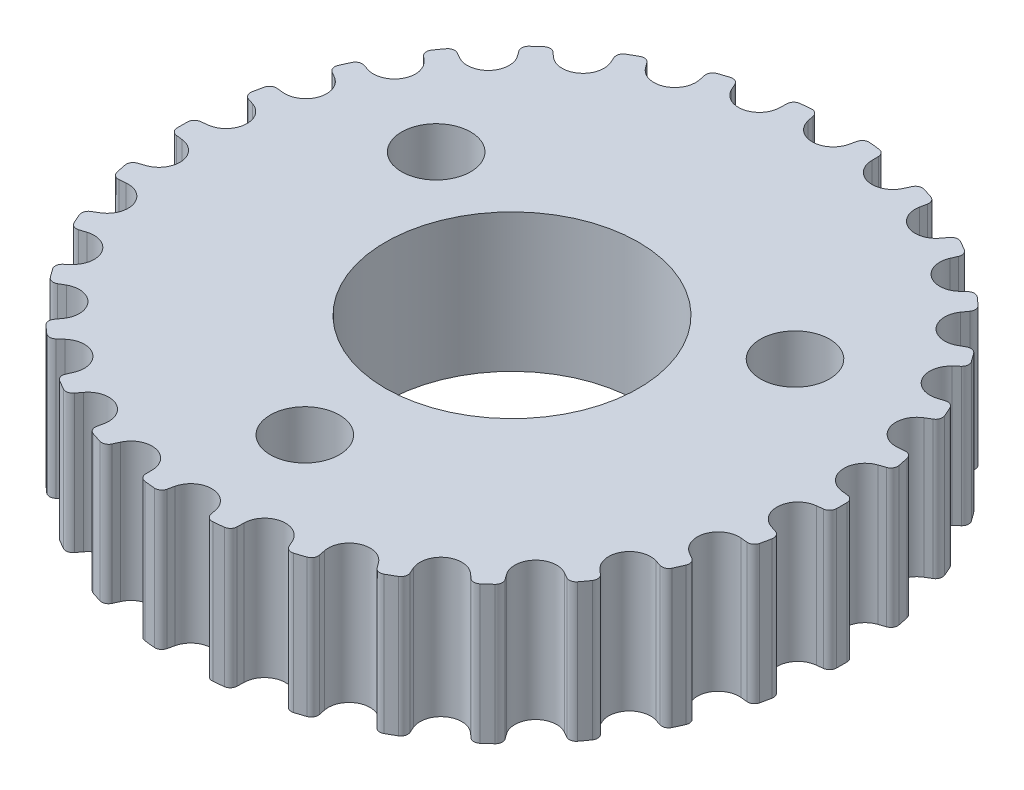
SolidWorks part; units mm, degrees
material "Acrylic (Medium-high impact)"
ref_plane "Front Plane" through (0, 0, 0) normal (0, 0, 1) x (1, 0, 0)
ref_plane "Top Plane" through (0, 0, 0) normal (0, 1, 0) x (1, 0, 0)
ref_plane "Right Plane" through (0, 0, 0) normal (1, 0, 0) x (0, 0, -1)
sketch "Sketch1" plane through (0, 0, 0) normal (0, 1, 0) x (1, 0, 0)
  circle A0 centre (0, 0) radius 14.3239
  dimension "D1" = 28.6479
extrude "Boss-Extrude1" add sketch "Sketch1" along normal blind 6
sketch "Sketch2" plane through (0, 6, 0) normal (0, 1, 0) x (1, 0, 0)
  line L0 (0, 0) -> (0, 14.3239) construction
  line L1 (-0.8883, 13.7564) -> (-0.95, 14.0339)
  line L2 (-2.9781, 14.0109) -> (-2.9781, 14.3239)
  line L3 (-2.9781, 14.3239) -> (2.9781, 14.3239)
  line L4 (0.8883, 13.7564) -> (0.95, 14.0339)
  line L5 (2.9781, 14.0109) -> (2.9781, 14.3239)
  circle A0 centre (0, 0) radius 14.3239 construction
  arc A1 (0.8883, 13.7564) -> (-0.8883, 13.7564) centre (0, 13.9539) cw
  arc A2 (-0.95, 14.0339) -> (-1.2694, 14.2676) centre (-1.2428, 13.9688) ccw
  arc A4 (0.95, 14.0339) -> (1.2694, 14.2676) centre (1.2428, 13.9688) cw
  arc A5 (-1.2694, 14.2676) -> (-2.9781, 14.0109) centre (0, 0) ccw
  arc A6 (1.2694, 14.2676) -> (2.9781, 14.0109) centre (0, 0) cw
  circle A8 centre (0, 0) radius 14.3239 construction
  point P11 (0, 14.3239)
  point P19 (0, 13.0439)
  dimension "D3" = 0.3
  dimension "D5" = 0.91
  dimension "D2" = 0.95
  dimension "D4" = 1.28
  dimension "D6" = 12
extrude "Cut-Extrude1" cut sketch "Sketch2" against normal through all
pattern_circular "CirPattern1" count 30 over 360 about axis through (0, 6, 0) along (0, -1, 0) of "Cut-Extrude1"
sketch "Sketch3" plane through (0, 0, 0) normal (0, -1, 0) x (1, 0, 0)
  circle A0 centre (0, 0) radius 5.5
  dimension "D1" = 11
extrude "Cut-Extrude2" cut sketch "Sketch3" against normal through all
sketch "Sketch4" plane through (0, 0, 0) normal (0, -1, 0) x (1, 0, 0)
  line L0 (0, 0) -> (0, 9) construction
  circle A0 centre (0, 9) radius 1.5
  circle A1 centre (7.7942, -4.5) radius 1.5
  circle A2 centre (-7.7942, -4.5) radius 1.5
  point P14 (0, 0)
  dimension "D1" = 3
  dimension "D2" = 9
  dimension "D3" = 3
extrude "Cut-Extrude3" cut sketch "Sketch4" against normal through all
sketch "Sketch5" plane through (0, 0, 0) normal (0, -1, 0) x (1, 0, 0)
  line L60 (8.7383, -10.682) -> (8.9513, -10.8702)
  line L61 (8.7383, -10.682) -> (8.9513, -10.8702)
  line L62 (9.875, -10.0385) -> (9.7101, -9.807)
  line L63 (9.875, -10.0385) -> (9.7101, -9.807)
  line L64 (12.5987, 6.2896) -> (12.3276, 6.2043)
  line L65 (12.5987, 6.2896) -> (12.3276, 6.2043)
  line L66 (11.5369, 7.5738) -> (11.7463, 7.766)
  line L67 (11.5369, 7.5738) -> (11.7463, 7.766)
  line L68 (-3.638, 13.3126) -> (-3.7561, 13.5712)
  line L69 (-3.638, 13.3126) -> (-3.7561, 13.5712)
  line L70 (-4.9382, 13.1871) -> (-4.8817, 12.9085)
  line L71 (-4.9382, 13.1871) -> (-4.8817, 12.9085)
  line L72 (-11.7463, 7.766) -> (-11.5369, 7.5738)
  line L73 (-11.7463, 7.766) -> (-11.5369, 7.5738)
  line L74 (-12.3276, 6.2043) -> (-12.5987, 6.2896)
  line L75 (-12.3276, 6.2043) -> (-12.5987, 6.2896)
  line L76 (-13.1043, 5.1541) -> (-12.8594, 5.0097)
  line L77 (-13.1043, 5.1541) -> (-12.8594, 5.0097)
  line L78 (-13.3481, 3.5057) -> (-13.6311, 3.5327)
  line L79 (-13.3481, 3.5057) -> (-13.6311, 3.5327)
  line L80 (-13.8895, 2.3169) -> (-13.62, 2.2266)
  line L81 (-13.8895, 2.3169) -> (-13.62, 2.2266)
  line L82 (-13.7853, 0.6538) -> (-14.0677, 0.6215)
  line L83 (-13.7853, 0.6538) -> (-14.0677, 0.6215)
  line L84 (-14.0677, -0.6215) -> (-13.7853, -0.6538)
  line L85 (-14.0677, -0.6215) -> (-13.7853, -0.6538)
  line L86 (-13.62, -2.2266) -> (-13.8895, -2.3169)
  line L87 (-13.62, -2.2266) -> (-13.8895, -2.3169)
  line L88 (-13.6311, -3.5327) -> (-13.3481, -3.5057)
  line L89 (-13.6311, -3.5327) -> (-13.3481, -3.5057)
  line L90 (-12.8594, -5.0097) -> (-13.1043, -5.1541)
  line L91 (-12.8594, -5.0097) -> (-13.1043, -5.1541)
  line L92 (-12.5987, -6.2896) -> (-12.3276, -6.2043)
  line L93 (-12.5987, -6.2896) -> (-12.3276, -6.2043)
  line L94 (-11.5369, -7.5738) -> (-11.7463, -7.766)
  line L95 (-11.5369, -7.5738) -> (-11.7463, -7.766)
  line L96 (-11.0157, -8.7716) -> (-10.7682, -8.6318)
  line L97 (-11.0157, -8.7716) -> (-10.7682, -8.6318)
  line L98 (-9.7101, -9.807) -> (-9.875, -10.0385)
  line L99 (-9.7101, -9.807) -> (-9.875, -10.0385)
  line L100 (-8.9513, -10.8702) -> (-8.7383, -10.682)
  line L101 (-8.9513, -10.8702) -> (-8.7383, -10.682)
  line L102 (-7.4589, -11.6115) -> (-7.5721, -11.8722)
  line L103 (-7.4589, -11.6115) -> (-7.5721, -11.8722)
  line L104 (-6.4956, -12.4937) -> (-6.3264, -12.2653)
  line L105 (-6.4956, -12.4937) -> (-6.3264, -12.2653)
  line L106 (-4.8817, -12.9085) -> (-4.9382, -13.1871)
  line L107 (-4.8817, -12.9085) -> (-4.9382, -13.1871)
  line L108 (-3.7561, -13.5712) -> (-3.638, -13.3126)
  line L109 (-3.7561, -13.5712) -> (-3.638, -13.3126)
  line L110 (-2.0912, -13.6414) -> (-2.0886, -13.9257)
  line L111 (-2.0912, -13.6414) -> (-2.0886, -13.9257)
  line L120 (6.3264, -12.2653) -> (6.4956, -12.4937)
  line L121 (7.5721, -11.8722) -> (7.4589, -11.6115)
  line L124 (10.7682, -8.6318) -> (11.0157, -8.7716)
  line L125 (11.7463, -7.766) -> (11.5369, -7.5738)
  line L126 (12.3276, -6.2043) -> (12.5987, -6.2896)
  line L127 (13.1043, -5.1541) -> (12.8594, -5.0097)
  line L128 (13.3481, -3.5057) -> (13.6311, -3.5327)
  line L129 (13.8895, -2.3169) -> (13.62, -2.2266)
  line L130 (13.7853, -0.6538) -> (14.0677, -0.6215)
  line L131 (14.0677, 0.6215) -> (13.7853, 0.6538)
  line L132 (13.62, 2.2266) -> (13.8895, 2.3169)
  line L133 (13.6311, 3.5327) -> (13.3481, 3.5057)
  line L134 (12.8594, 5.0097) -> (13.1043, 5.1541)
  line L137 (11.0157, 8.7716) -> (10.7682, 8.6318)
  line L138 (9.7101, 9.807) -> (9.875, 10.0385)
  line L139 (8.9513, 10.8702) -> (8.7383, 10.682)
  line L140 (7.4589, 11.6115) -> (7.5721, 11.8722)
  line L141 (6.4956, 12.4937) -> (6.3264, 12.2653)
  line L142 (4.8817, 12.9085) -> (4.9382, 13.1871)
  line L143 (3.7561, 13.5712) -> (3.638, 13.3126)
  line L144 (2.0912, 13.6414) -> (2.0886, 13.9257)
  line L145 (0.8524, 14.0556) -> (0.7907, 13.7781)
  line L146 (-0.7907, 13.7781) -> (-0.8524, 14.0556)
  line L147 (-2.0886, 13.9257) -> (-2.0912, 13.6414)
  line L150 (-6.3264, 12.2653) -> (-6.4956, 12.4937)
  line L151 (-7.5721, 11.8722) -> (-7.4589, 11.6115)
  line L152 (-8.7383, 10.682) -> (-8.9513, 10.8702)
  line L153 (-9.875, 10.0385) -> (-9.7101, 9.807)
  line L154 (-10.7682, 8.6318) -> (-11.0157, 8.7716)
  line L175 (-0.8524, -14.0556) -> (-0.7907, -13.7781)
  line L176 (0.7907, -13.7781) -> (0.8524, -14.0556)
  line L177 (2.0886, -13.9257) -> (2.0912, -13.6414)
  line L178 (3.638, -13.3126) -> (3.7561, -13.5712)
  line L179 (4.9382, -13.1871) -> (4.8817, -12.9085)
  line L180 (6.3264, -12.2653) -> (6.4956, -12.4937)
  line L181 (7.5721, -11.8722) -> (7.4589, -11.6115)
  line L184 (10.7682, -8.6318) -> (11.0157, -8.7716)
  line L185 (11.7463, -7.766) -> (11.5369, -7.5738)
  line L186 (12.3276, -6.2043) -> (12.5987, -6.2896)
  line L187 (13.1043, -5.1541) -> (12.8594, -5.0097)
  line L188 (13.3481, -3.5057) -> (13.6311, -3.5327)
  line L189 (13.8895, -2.3169) -> (13.62, -2.2266)
  line L190 (13.7853, -0.6538) -> (14.0677, -0.6215)
  line L191 (14.0677, 0.6215) -> (13.7853, 0.6538)
  line L192 (13.62, 2.2266) -> (13.8895, 2.3169)
  line L193 (13.6311, 3.5327) -> (13.3481, 3.5057)
  line L194 (12.8594, 5.0097) -> (13.1043, 5.1541)
  line L197 (11.0157, 8.7716) -> (10.7682, 8.6318)
  line L198 (9.7101, 9.807) -> (9.875, 10.0385)
  line L199 (8.9513, 10.8702) -> (8.7383, 10.682)
  line L200 (7.4589, 11.6115) -> (7.5721, 11.8722)
  line L201 (6.4956, 12.4937) -> (6.3264, 12.2653)
  line L202 (4.8817, 12.9085) -> (4.9382, 13.1871)
  line L203 (3.7561, 13.5712) -> (3.638, 13.3126)
  line L204 (2.0912, 13.6414) -> (2.0886, 13.9257)
  line L205 (0.8524, 14.0556) -> (0.7907, 13.7781)
  line L206 (-0.7907, 13.7781) -> (-0.8524, 14.0556)
  line L207 (-2.0886, 13.9257) -> (-2.0912, 13.6414)
  line L210 (-6.3264, 12.2653) -> (-6.4956, 12.4937)
  line L211 (-7.5721, 11.8722) -> (-7.4589, 11.6115)
  line L212 (-8.7383, 10.682) -> (-8.9513, 10.8702)
  line L213 (-9.875, 10.0385) -> (-9.7101, 9.807)
  line L214 (-10.7682, 8.6318) -> (-11.0157, 8.7716)
  line L235 (-0.8524, -14.0556) -> (-0.7907, -13.7781)
  line L236 (0.7907, -13.7781) -> (0.8524, -14.0556)
  line L237 (2.0886, -13.9257) -> (2.0912, -13.6414)
  line L238 (3.638, -13.3126) -> (3.7561, -13.5712)
  line L239 (4.9382, -13.1871) -> (4.8817, -12.9085)
  arc A76 (8.9513, -10.8702) -> (9.479, -10.8719) centre (9.2161, -10.5704) ccw
  arc A77 (8.9513, -10.8702) -> (9.479, -10.8719) centre (9.2161, -10.5704) ccw
  arc A78 (9.479, -10.8719) -> (9.8216, -10.5635) centre (0, 0) ccw
  arc A79 (9.479, -10.8719) -> (9.8216, -10.5635) centre (0, 0) ccw
  arc A80 (9.8216, -10.5635) -> (9.875, -10.0385) centre (9.5492, -10.2705) ccw
  arc A81 (9.8216, -10.5635) -> (9.875, -10.0385) centre (9.5492, -10.2705) ccw
  circle A120 centre (0, 0) radius 13.0439
  arc A121 (-0.8883, 13.7564) -> (0.8883, 13.7564) centre (0, 13.9539) ccw construction
  arc A128 (11.5369, 7.5738) -> (12.3276, 6.2043) centre (12.0845, 6.977) ccw
  arc A129 (11.5369, 7.5738) -> (12.3276, 6.2043) centre (12.0845, 6.977) ccw
  arc A130 (-3.7561, 13.5712) -> (-4.2375, 13.7875) centre (-4.12, 13.4051) ccw
  arc A131 (-3.7561, 13.5712) -> (-4.2375, 13.7875) centre (-4.12, 13.4051) ccw
  arc A132 (-4.2375, 13.7875) -> (-4.6759, 13.645) centre (0, 0) ccw
  arc A133 (-4.2375, 13.7875) -> (-4.6759, 13.645) centre (0, 0) ccw
  arc A134 (-4.6759, 13.645) -> (-4.9382, 13.1871) centre (-4.5462, 13.2666) ccw
  arc A135 (-4.6759, 13.645) -> (-4.9382, 13.1871) centre (-4.5462, 13.2666) ccw
  arc A136 (-11.8032, 8.2906) -> (-11.7463, 7.766) centre (-11.4759, 8.0607) ccw
  arc A137 (-11.8032, 8.2906) -> (-11.7463, 7.766) centre (-11.4759, 8.0607) ccw
  arc A138 (-12.3276, 6.2043) -> (-11.5369, 7.5738) centre (-12.0845, 6.977) ccw
  arc A139 (-12.3276, 6.2043) -> (-11.5369, 7.5738) centre (-12.0845, 6.977) ccw
  arc A140 (-12.5987, 6.2896) -> (-13.0815, 6.0766) centre (-12.7187, 5.908) ccw
  arc A141 (-12.5987, 6.2896) -> (-13.0815, 6.0766) centre (-12.7187, 5.908) ccw
  arc A142 (-13.0815, 6.0766) -> (-13.269, 5.6554) centre (0, 0) ccw
  arc A143 (-13.0815, 6.0766) -> (-13.269, 5.6554) centre (0, 0) ccw
  arc A144 (-13.269, 5.6554) -> (-13.1043, 5.1541) centre (-12.901, 5.4986) ccw
  arc A145 (-13.269, 5.6554) -> (-13.1043, 5.1541) centre (-12.901, 5.4986) ccw
  arc A146 (-13.3481, 3.5057) -> (-12.8594, 5.0097) centre (-13.271, 4.312) ccw
  arc A147 (-13.3481, 3.5057) -> (-12.8594, 5.0097) centre (-13.271, 4.312) ccw
  arc A148 (-13.6311, 3.5327) -> (-14.059, 3.224) centre (-13.6691, 3.1346) ccw
  arc A149 (-13.6311, 3.5327) -> (-14.059, 3.224) centre (-13.6691, 3.1346) ccw
  arc A150 (-14.059, 3.224) -> (-14.1549, 2.7731) centre (0, 0) ccw
  arc A151 (-14.059, 3.224) -> (-14.1549, 2.7731) centre (0, 0) ccw
  arc A152 (-14.1549, 2.7731) -> (-13.8895, 2.3169) centre (-13.7623, 2.6962) ccw
  arc A153 (-14.1549, 2.7731) -> (-13.8895, 2.3169) centre (-13.7623, 2.6962) ccw
  arc A154 (-13.7853, 0.6538) -> (-13.62, 2.2266) centre (-13.8775, 1.4586) ccw
  arc A155 (-13.7853, 0.6538) -> (-13.62, 2.2266) centre (-13.8775, 1.4586) ccw
  arc A156 (-14.0677, 0.6215) -> (-14.4221, 0.2305) centre (-14.0222, 0.2241) ccw
  arc A157 (-14.0677, 0.6215) -> (-14.4221, 0.2305) centre (-14.0222, 0.2241) ccw
  arc A158 (-14.4221, 0.2305) -> (-14.4221, -0.2305) centre (0, 0) ccw
  arc A159 (-14.4221, 0.2305) -> (-14.4221, -0.2305) centre (0, 0) ccw
  arc A160 (-14.4221, -0.2305) -> (-14.0677, -0.6215) centre (-14.0222, -0.2241) ccw
  arc A161 (-14.4221, -0.2305) -> (-14.0677, -0.6215) centre (-14.0222, -0.2241) ccw
  arc A162 (-13.62, -2.2266) -> (-13.7853, -0.6538) centre (-13.8775, -1.4586) ccw
  arc A163 (-13.62, -2.2266) -> (-13.7853, -0.6538) centre (-13.8775, -1.4586) ccw
  arc A164 (-13.8895, -2.3169) -> (-14.1549, -2.7731) centre (-13.7623, -2.6962) ccw
  arc A165 (-13.8895, -2.3169) -> (-14.1549, -2.7731) centre (-13.7623, -2.6962) ccw
  arc A166 (-14.1549, -2.7731) -> (-14.059, -3.224) centre (0, 0) ccw
  arc A167 (-14.1549, -2.7731) -> (-14.059, -3.224) centre (0, 0) ccw
  arc A168 (-14.059, -3.224) -> (-13.6311, -3.5327) centre (-13.6691, -3.1346) ccw
  arc A169 (-14.059, -3.224) -> (-13.6311, -3.5327) centre (-13.6691, -3.1346) ccw
  arc A170 (-12.8594, -5.0097) -> (-13.3481, -3.5057) centre (-13.271, -4.312) ccw
  arc A171 (-12.8594, -5.0097) -> (-13.3481, -3.5057) centre (-13.271, -4.312) ccw
  arc A172 (-13.1043, -5.1541) -> (-13.269, -5.6554) centre (-12.901, -5.4986) ccw
  arc A173 (-13.1043, -5.1541) -> (-13.269, -5.6554) centre (-12.901, -5.4986) ccw
  arc A174 (-13.269, -5.6554) -> (-13.0815, -6.0766) centre (0, 0) ccw
  arc A175 (-13.269, -5.6554) -> (-13.0815, -6.0766) centre (0, 0) ccw
  arc A176 (-13.0815, -6.0766) -> (-12.5987, -6.2896) centre (-12.7187, -5.908) ccw
  arc A177 (-13.0815, -6.0766) -> (-12.5987, -6.2896) centre (-12.7187, -5.908) ccw
  arc A178 (-11.5369, -7.5738) -> (-12.3276, -6.2043) centre (-12.0845, -6.977) ccw
  arc A179 (-11.5369, -7.5738) -> (-12.3276, -6.2043) centre (-12.0845, -6.977) ccw
  arc A180 (-11.7463, -7.766) -> (-11.8032, -8.2906) centre (-11.4759, -8.0607) ccw
  arc A181 (-11.7463, -7.766) -> (-11.8032, -8.2906) centre (-11.4759, -8.0607) ccw
  arc A182 (-11.8032, -8.2906) -> (-11.5323, -8.6636) centre (0, 0) ccw
  arc A183 (-11.8032, -8.2906) -> (-11.5323, -8.6636) centre (0, 0) ccw
  arc A184 (-11.5323, -8.6636) -> (-11.0157, -8.7716) centre (-11.2124, -8.4233) ccw
  arc A185 (-11.5323, -8.6636) -> (-11.0157, -8.7716) centre (-11.2124, -8.4233) ccw
  arc A186 (-9.7101, -9.807) -> (-10.7682, -8.6318) centre (-10.3698, -9.337) ccw
  arc A187 (-9.7101, -9.807) -> (-10.7682, -8.6318) centre (-10.3698, -9.337) ccw
  arc A188 (-9.875, -10.0385) -> (-9.8216, -10.5635) centre (-9.5492, -10.2705) ccw
  arc A189 (-9.875, -10.0385) -> (-9.8216, -10.5635) centre (-9.5492, -10.2705) ccw
  arc A190 (-9.8216, -10.5635) -> (-9.479, -10.8719) centre (0, 0) ccw
  arc A191 (-9.8216, -10.5635) -> (-9.479, -10.8719) centre (0, 0) ccw
  arc A192 (-9.479, -10.8719) -> (-8.9513, -10.8702) centre (-9.2161, -10.5704) ccw
  arc A193 (-9.479, -10.8719) -> (-8.9513, -10.8702) centre (-9.2161, -10.5704) ccw
  arc A194 (-7.4589, -11.6115) -> (-8.7383, -10.682) centre (-8.2019, -11.289) ccw
  arc A195 (-7.4589, -11.6115) -> (-8.7383, -10.682) centre (-8.2019, -11.289) ccw
  arc A196 (-7.5721, -11.8722) -> (-7.4107, -12.3747) centre (-7.2051, -12.0315) ccw
  arc A197 (-7.5721, -11.8722) -> (-7.4107, -12.3747) centre (-7.2051, -12.0315) ccw
  arc A198 (-7.4107, -12.3747) -> (-7.0114, -12.6052) centre (0, 0) ccw
  arc A199 (-7.4107, -12.3747) -> (-7.0114, -12.6052) centre (0, 0) ccw
  arc A200 (-7.0114, -12.6052) -> (-6.4956, -12.4937) centre (-6.817, -12.2556) ccw
  arc A201 (-7.0114, -12.6052) -> (-6.4956, -12.4937) centre (-6.817, -12.2556) ccw
  arc A202 (-4.8817, -12.9085) -> (-6.3264, -12.2653) centre (-5.6756, -12.7476) ccw
  arc A203 (-4.8817, -12.9085) -> (-6.3264, -12.2653) centre (-5.6756, -12.7476) ccw
  arc A204 (-4.9382, -13.1871) -> (-4.6759, -13.645) centre (-4.5462, -13.2666) ccw
  arc A205 (-4.9382, -13.1871) -> (-4.6759, -13.645) centre (-4.5462, -13.2666) ccw
  arc A206 (-4.6759, -13.645) -> (-4.2375, -13.7875) centre (0, 0) ccw
  arc A207 (-4.6759, -13.645) -> (-4.2375, -13.7875) centre (0, 0) ccw
  arc A208 (-4.2375, -13.7875) -> (-3.7561, -13.5712) centre (-4.12, -13.4051) ccw
  arc A209 (-4.2375, -13.7875) -> (-3.7561, -13.5712) centre (-4.12, -13.4051) ccw
  arc A210 (-2.0912, -13.6414) -> (-3.638, -13.3126) centre (-2.9012, -13.649) ccw
  arc A211 (-2.0912, -13.6414) -> (-3.638, -13.3126) centre (-2.9012, -13.649) ccw
  arc A212 (-2.0886, -13.9257) -> (-1.7367, -14.319) centre (-1.6886, -13.9219) ccw
  arc A213 (-2.0886, -13.9257) -> (-1.7367, -14.319) centre (-1.6886, -13.9219) ccw
  arc A214 (-1.7367, -14.319) -> (-1.2783, -14.3672) centre (0, 0) ccw
  arc A215 (-1.7367, -14.319) -> (-1.2783, -14.3672) centre (0, 0) ccw
  arc A240 (6.4956, -12.4937) -> (7.0114, -12.6052) centre (6.817, -12.2556) ccw
  arc A241 (7.0114, -12.6052) -> (7.4107, -12.3747) centre (0, 0) ccw
  arc A242 (7.4107, -12.3747) -> (7.5721, -11.8722) centre (7.2051, -12.0315) ccw
  arc A243 (8.7383, -10.682) -> (7.4589, -11.6115) centre (8.2019, -11.289) ccw
  arc A247 (10.7682, -8.6318) -> (9.7101, -9.807) centre (10.3698, -9.337) ccw
  arc A248 (11.0157, -8.7716) -> (11.5323, -8.6636) centre (11.2124, -8.4233) ccw
  arc A249 (11.5323, -8.6636) -> (11.8032, -8.2906) centre (0, 0) ccw
  arc A250 (11.8032, -8.2906) -> (11.7463, -7.766) centre (11.4759, -8.0607) ccw
  arc A251 (12.3276, -6.2043) -> (11.5369, -7.5738) centre (12.0845, -6.977) ccw
  arc A252 (12.5987, -6.2896) -> (13.0815, -6.0766) centre (12.7187, -5.908) ccw
  arc A253 (13.0815, -6.0766) -> (13.269, -5.6554) centre (0, 0) ccw
  arc A254 (13.269, -5.6554) -> (13.1043, -5.1541) centre (12.901, -5.4986) ccw
  arc A255 (13.3481, -3.5057) -> (12.8594, -5.0097) centre (13.271, -4.312) ccw
  arc A256 (13.6311, -3.5327) -> (14.059, -3.224) centre (13.6691, -3.1346) ccw
  arc A257 (14.059, -3.224) -> (14.1549, -2.7731) centre (0, 0) ccw
  arc A258 (14.1549, -2.7731) -> (13.8895, -2.3169) centre (13.7623, -2.6962) ccw
  arc A259 (13.7853, -0.6538) -> (13.62, -2.2266) centre (13.8775, -1.4586) ccw
  arc A260 (14.0677, -0.6215) -> (14.4221, -0.2305) centre (14.0222, -0.2241) ccw
  arc A261 (14.4221, -0.2305) -> (14.4221, 0.2305) centre (0, 0) ccw
  arc A262 (14.4221, 0.2305) -> (14.0677, 0.6215) centre (14.0222, 0.2241) ccw
  arc A263 (13.62, 2.2266) -> (13.7853, 0.6538) centre (13.8775, 1.4586) ccw
  arc A264 (13.8895, 2.3169) -> (14.1549, 2.7731) centre (13.7623, 2.6962) ccw
  arc A265 (14.1549, 2.7731) -> (14.059, 3.224) centre (0, 0) ccw
  arc A266 (14.059, 3.224) -> (13.6311, 3.5327) centre (13.6691, 3.1346) ccw
  arc A267 (12.8594, 5.0097) -> (13.3481, 3.5057) centre (13.271, 4.312) ccw
  arc A268 (13.1043, 5.1541) -> (13.269, 5.6554) centre (12.901, 5.4986) ccw
  arc A269 (13.269, 5.6554) -> (13.0815, 6.0766) centre (0, 0) ccw
  arc A270 (13.0815, 6.0766) -> (12.5987, 6.2896) centre (12.7187, 5.908) ccw
  arc A272 (11.7463, 7.766) -> (11.8032, 8.2906) centre (11.4759, 8.0607) ccw
  arc A273 (11.8032, 8.2906) -> (11.5323, 8.6636) centre (0, 0) ccw
  arc A274 (11.5323, 8.6636) -> (11.0157, 8.7716) centre (11.2124, 8.4233) ccw
  arc A275 (9.7101, 9.807) -> (10.7682, 8.6318) centre (10.3698, 9.337) ccw
  arc A276 (9.875, 10.0385) -> (9.8216, 10.5635) centre (9.5492, 10.2705) ccw
  arc A277 (9.8216, 10.5635) -> (9.479, 10.8719) centre (0, 0) ccw
  arc A278 (9.479, 10.8719) -> (8.9513, 10.8702) centre (9.2161, 10.5704) ccw
  arc A279 (7.4589, 11.6115) -> (8.7383, 10.682) centre (8.2019, 11.289) ccw
  arc A280 (7.5721, 11.8722) -> (7.4107, 12.3747) centre (7.2051, 12.0315) ccw
  arc A281 (7.4107, 12.3747) -> (7.0114, 12.6052) centre (0, 0) ccw
  arc A282 (7.0114, 12.6052) -> (6.4956, 12.4937) centre (6.817, 12.2556) ccw
  arc A283 (4.8817, 12.9085) -> (6.3264, 12.2653) centre (5.6756, 12.7476) ccw
  arc A284 (4.9382, 13.1871) -> (4.6759, 13.645) centre (4.5462, 13.2666) ccw
  arc A285 (4.6759, 13.645) -> (4.2375, 13.7875) centre (0, 0) ccw
  arc A286 (4.2375, 13.7875) -> (3.7561, 13.5712) centre (4.12, 13.4051) ccw
  arc A287 (2.0912, 13.6414) -> (3.638, 13.3126) centre (2.9012, 13.649) ccw
  arc A288 (2.0886, 13.9257) -> (1.7367, 14.319) centre (1.6886, 13.9219) ccw
  arc A289 (1.7367, 14.319) -> (1.2783, 14.3672) centre (0, 0) ccw
  arc A290 (1.2783, 14.3672) -> (0.8524, 14.0556) centre (1.2428, 13.9688) ccw
  arc A291 (-0.7907, 13.7781) -> (0.7907, 13.7781) centre (0, 13.9539) ccw
  arc A292 (-0.8524, 14.0556) -> (-1.2783, 14.3672) centre (-1.2428, 13.9688) ccw
  arc A293 (-1.2783, 14.3672) -> (-1.7367, 14.319) centre (0, 0) ccw
  arc A294 (-1.7367, 14.319) -> (-2.0886, 13.9257) centre (-1.6886, 13.9219) ccw
  arc A295 (-3.638, 13.3126) -> (-2.0912, 13.6414) centre (-2.9012, 13.649) ccw
  arc A299 (-6.3264, 12.2653) -> (-4.8817, 12.9085) centre (-5.6756, 12.7476) ccw
  arc A300 (-6.4956, 12.4937) -> (-7.0114, 12.6052) centre (-6.817, 12.2556) ccw
  arc A301 (-7.0114, 12.6052) -> (-7.4107, 12.3747) centre (0, 0) ccw
  arc A302 (-7.4107, 12.3747) -> (-7.5721, 11.8722) centre (-7.2051, 12.0315) ccw
  arc A303 (-8.7383, 10.682) -> (-7.4589, 11.6115) centre (-8.2019, 11.289) ccw
  arc A304 (-8.9513, 10.8702) -> (-9.479, 10.8719) centre (-9.2161, 10.5704) ccw
  arc A305 (-9.479, 10.8719) -> (-9.8216, 10.5635) centre (0, 0) ccw
  arc A306 (-9.8216, 10.5635) -> (-9.875, 10.0385) centre (-9.5492, 10.2705) ccw
  arc A307 (-10.7682, 8.6318) -> (-9.7101, 9.807) centre (-10.3698, 9.337) ccw
  arc A308 (-11.0157, 8.7716) -> (-11.5323, 8.6636) centre (-11.2124, 8.4233) ccw
  arc A309 (-11.5323, 8.6636) -> (-11.8032, 8.2906) centre (0, 0) ccw
  arc A350 (-1.2783, -14.3672) -> (-0.8524, -14.0556) centre (-1.2428, -13.9688) ccw
  arc A351 (0.7907, -13.7781) -> (-0.7907, -13.7781) centre (0, -13.9539) ccw
  arc A352 (0.8524, -14.0556) -> (1.2783, -14.3672) centre (1.2428, -13.9688) ccw
  arc A353 (1.2783, -14.3672) -> (1.7367, -14.319) centre (0, 0) ccw
  arc A354 (1.7367, -14.319) -> (2.0886, -13.9257) centre (1.6886, -13.9219) ccw
  arc A355 (3.638, -13.3126) -> (2.0912, -13.6414) centre (2.9012, -13.649) ccw
  arc A356 (3.7561, -13.5712) -> (4.2375, -13.7875) centre (4.12, -13.4051) ccw
  arc A357 (4.2375, -13.7875) -> (4.6759, -13.645) centre (0, 0) ccw
  arc A358 (4.6759, -13.645) -> (4.9382, -13.1871) centre (4.5462, -13.2666) ccw
  arc A359 (6.3264, -12.2653) -> (4.8817, -12.9085) centre (5.6756, -12.7476) ccw
  arc A360 (6.4956, -12.4937) -> (7.0114, -12.6052) centre (6.817, -12.2556) ccw
  arc A361 (7.0114, -12.6052) -> (7.4107, -12.3747) centre (0, 0) ccw
  arc A362 (7.4107, -12.3747) -> (7.5721, -11.8722) centre (7.2051, -12.0315) ccw
  arc A363 (8.7383, -10.682) -> (7.4589, -11.6115) centre (8.2019, -11.289) ccw
  arc A367 (10.7682, -8.6318) -> (9.7101, -9.807) centre (10.3698, -9.337) ccw
  arc A368 (11.0157, -8.7716) -> (11.5323, -8.6636) centre (11.2124, -8.4233) ccw
  arc A369 (11.5323, -8.6636) -> (11.8032, -8.2906) centre (0, 0) ccw
  arc A370 (11.8032, -8.2906) -> (11.7463, -7.766) centre (11.4759, -8.0607) ccw
  arc A371 (12.3276, -6.2043) -> (11.5369, -7.5738) centre (12.0845, -6.977) ccw
  arc A372 (12.5987, -6.2896) -> (13.0815, -6.0766) centre (12.7187, -5.908) ccw
  arc A373 (13.0815, -6.0766) -> (13.269, -5.6554) centre (0, 0) ccw
  arc A374 (13.269, -5.6554) -> (13.1043, -5.1541) centre (12.901, -5.4986) ccw
  arc A375 (13.3481, -3.5057) -> (12.8594, -5.0097) centre (13.271, -4.312) ccw
  arc A376 (13.6311, -3.5327) -> (14.059, -3.224) centre (13.6691, -3.1346) ccw
  arc A377 (14.059, -3.224) -> (14.1549, -2.7731) centre (0, 0) ccw
  arc A378 (14.1549, -2.7731) -> (13.8895, -2.3169) centre (13.7623, -2.6962) ccw
  arc A379 (13.7853, -0.6538) -> (13.62, -2.2266) centre (13.8775, -1.4586) ccw
  arc A380 (14.0677, -0.6215) -> (14.4221, -0.2305) centre (14.0222, -0.2241) ccw
  arc A381 (14.4221, -0.2305) -> (14.4221, 0.2305) centre (0, 0) ccw
  arc A382 (14.4221, 0.2305) -> (14.0677, 0.6215) centre (14.0222, 0.2241) ccw
  arc A383 (13.62, 2.2266) -> (13.7853, 0.6538) centre (13.8775, 1.4586) ccw
  arc A384 (13.8895, 2.3169) -> (14.1549, 2.7731) centre (13.7623, 2.6962) ccw
  arc A385 (14.1549, 2.7731) -> (14.059, 3.224) centre (0, 0) ccw
  arc A386 (14.059, 3.224) -> (13.6311, 3.5327) centre (13.6691, 3.1346) ccw
  arc A387 (12.8594, 5.0097) -> (13.3481, 3.5057) centre (13.271, 4.312) ccw
  arc A388 (13.1043, 5.1541) -> (13.269, 5.6554) centre (12.901, 5.4986) ccw
  arc A389 (13.269, 5.6554) -> (13.0815, 6.0766) centre (0, 0) ccw
  arc A390 (13.0815, 6.0766) -> (12.5987, 6.2896) centre (12.7187, 5.908) ccw
  arc A392 (11.7463, 7.766) -> (11.8032, 8.2906) centre (11.4759, 8.0607) ccw
  arc A393 (11.8032, 8.2906) -> (11.5323, 8.6636) centre (0, 0) ccw
  arc A394 (11.5323, 8.6636) -> (11.0157, 8.7716) centre (11.2124, 8.4233) ccw
  arc A395 (9.7101, 9.807) -> (10.7682, 8.6318) centre (10.3698, 9.337) ccw
  arc A396 (9.875, 10.0385) -> (9.8216, 10.5635) centre (9.5492, 10.2705) ccw
  arc A397 (9.8216, 10.5635) -> (9.479, 10.8719) centre (0, 0) ccw
  arc A398 (9.479, 10.8719) -> (8.9513, 10.8702) centre (9.2161, 10.5704) ccw
  arc A399 (7.4589, 11.6115) -> (8.7383, 10.682) centre (8.2019, 11.289) ccw
  arc A400 (7.5721, 11.8722) -> (7.4107, 12.3747) centre (7.2051, 12.0315) ccw
  arc A401 (7.4107, 12.3747) -> (7.0114, 12.6052) centre (0, 0) ccw
  arc A402 (7.0114, 12.6052) -> (6.4956, 12.4937) centre (6.817, 12.2556) ccw
  arc A403 (4.8817, 12.9085) -> (6.3264, 12.2653) centre (5.6756, 12.7476) ccw
  arc A404 (4.9382, 13.1871) -> (4.6759, 13.645) centre (4.5462, 13.2666) ccw
  arc A405 (4.6759, 13.645) -> (4.2375, 13.7875) centre (0, 0) ccw
  arc A406 (4.2375, 13.7875) -> (3.7561, 13.5712) centre (4.12, 13.4051) ccw
  arc A407 (2.0912, 13.6414) -> (3.638, 13.3126) centre (2.9012, 13.649) ccw
  arc A408 (2.0886, 13.9257) -> (1.7367, 14.319) centre (1.6886, 13.9219) ccw
  arc A409 (1.7367, 14.319) -> (1.2783, 14.3672) centre (0, 0) ccw
  arc A410 (1.2783, 14.3672) -> (0.8524, 14.0556) centre (1.2428, 13.9688) ccw
  arc A411 (-0.7907, 13.7781) -> (0.7907, 13.7781) centre (0, 13.9539) ccw
  arc A412 (-0.8524, 14.0556) -> (-1.2783, 14.3672) centre (-1.2428, 13.9688) ccw
  arc A413 (-1.2783, 14.3672) -> (-1.7367, 14.319) centre (0, 0) ccw
  arc A414 (-1.7367, 14.319) -> (-2.0886, 13.9257) centre (-1.6886, 13.9219) ccw
  arc A415 (-3.638, 13.3126) -> (-2.0912, 13.6414) centre (-2.9012, 13.649) ccw
  arc A419 (-6.3264, 12.2653) -> (-4.8817, 12.9085) centre (-5.6756, 12.7476) ccw
  arc A420 (-6.4956, 12.4937) -> (-7.0114, 12.6052) centre (-6.817, 12.2556) ccw
  arc A421 (-7.0114, 12.6052) -> (-7.4107, 12.3747) centre (0, 0) ccw
  arc A422 (-7.4107, 12.3747) -> (-7.5721, 11.8722) centre (-7.2051, 12.0315) ccw
  arc A423 (-8.7383, 10.682) -> (-7.4589, 11.6115) centre (-8.2019, 11.289) ccw
  arc A424 (-8.9513, 10.8702) -> (-9.479, 10.8719) centre (-9.2161, 10.5704) ccw
  arc A425 (-9.479, 10.8719) -> (-9.8216, 10.5635) centre (0, 0) ccw
  arc A426 (-9.8216, 10.5635) -> (-9.875, 10.0385) centre (-9.5492, 10.2705) ccw
  arc A427 (-10.7682, 8.6318) -> (-9.7101, 9.807) centre (-10.3698, 9.337) ccw
  arc A428 (-11.0157, 8.7716) -> (-11.5323, 8.6636) centre (-11.2124, 8.4233) ccw
  arc A429 (-11.5323, 8.6636) -> (-11.8032, 8.2906) centre (0, 0) ccw
  arc A470 (-1.2783, -14.3672) -> (-0.8524, -14.0556) centre (-1.2428, -13.9688) ccw
  arc A471 (0.7907, -13.7781) -> (-0.7907, -13.7781) centre (0, -13.9539) ccw
  arc A472 (0.8524, -14.0556) -> (1.2783, -14.3672) centre (1.2428, -13.9688) ccw
  arc A473 (1.2783, -14.3672) -> (1.7367, -14.319) centre (0, 0) ccw
  arc A474 (1.7367, -14.319) -> (2.0886, -13.9257) centre (1.6886, -13.9219) ccw
  arc A475 (3.638, -13.3126) -> (2.0912, -13.6414) centre (2.9012, -13.649) ccw
  arc A476 (3.7561, -13.5712) -> (4.2375, -13.7875) centre (4.12, -13.4051) ccw
  arc A477 (4.2375, -13.7875) -> (4.6759, -13.645) centre (0, 0) ccw
  arc A478 (4.6759, -13.645) -> (4.9382, -13.1871) centre (4.5462, -13.2666) ccw
  arc A479 (6.3264, -12.2653) -> (4.8817, -12.9085) centre (5.6756, -12.7476) ccw
  dimension "D1" = 0.1
extrude "Boss-Extrude2" [suppressed] add sketch "Sketch5" against normal up to surface (5.8 mm away) up to face at (7.7942, 6, -6)
equation "\"smallPulleyTeeth\"= 15"
equation "\"largePulleyTeeth\"= 30"
equation "\"eighthThick\"= 3.0mm"
equation "\"D1@Sketch1\"=3*\"largePulleyTeeth\"/pi"
equation "\"D1@Boss-Extrude1\" = \"eighthThick\" * 2"
equation "\"D6@Sketch2\"=360/\"largePulleyTeeth\""
equation "\"quarterThick\"=6.0mm"
equation "\"D1@CirPattern1\"=\"largePulleyTeeth\""
equation "\"sixteenthThick\"= 1.7mm"
equation "\"OD\"= 145mm"
equation "\"puckAngle\"= 60.5deg"
equation "\"puckDiam\"= 76.5mm"
equation "\"axlePress\"= 5.9mm"
equation "\"press\"= 0.2mm"
equation "\"wheelClear\"= 0.3mm"
equation "\"10-32clear\"= 4.8mm"
equation "\"D1@Sketch4\"=\"4-40clear\""
equation "\"6-32clear\"= 3.3mm"
equation "\"8-32clear\"= 4.0mm"
equation "\"4-40clear\"= 3.0mm"
equation "\"wheelHeight\"= 22mm"
equation "\"wheelWell\"= 65mm"
